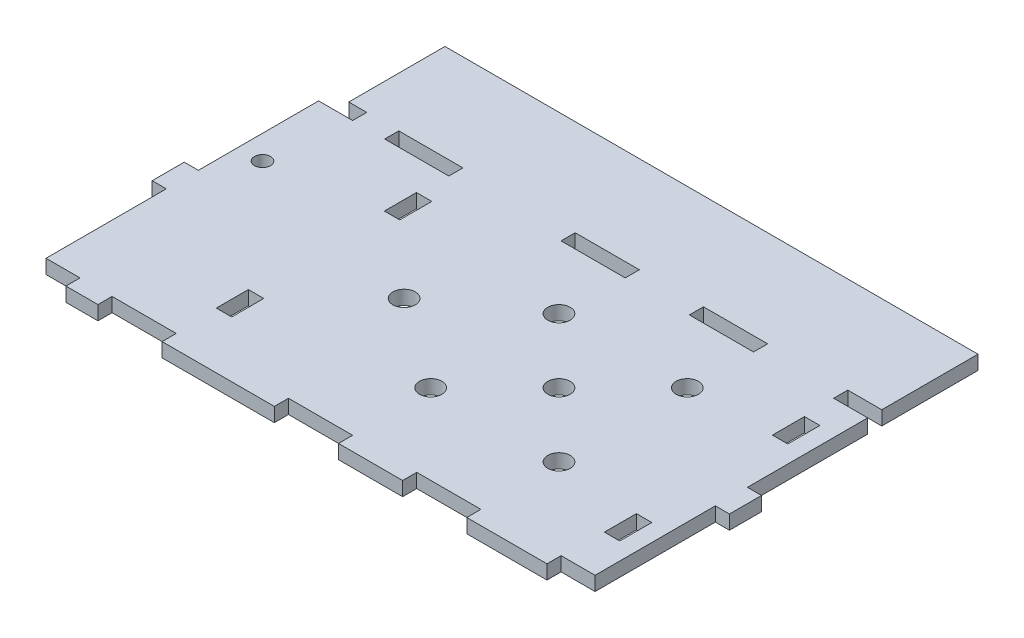
SolidWorks part; units mm, degrees
ref_plane "Front Plane" through (0, 0, 0) normal (0, 0, 1) x (1, 0, 0)
ref_plane "Top Plane" through (0, 0, 0) normal (0, 1, 0) x (1, 0, 0)
ref_plane "Right Plane" through (0, 0, 0) normal (1, 0, 0) x (0, 0, -1)
sketch "Sketch1" plane through (0, 0, 0) normal (0, 1, 0) x (1, 0, 0)
  line L0 (-108.712, 6.35) -> (-114.3, 6.35)
  line L2 (-108.712, -53.975) -> (-108.712, -6.35)
  line L4 (108.712, -53.975) -> (108.712, -6.35)
  line L5 (-108.712, -53.975) -> (108.712, 53.975) construction
  line L6 (-108.712, 53.975) -> (108.712, -53.975) construction
  line L7 (-114.3, 6.35) -> (-114.3, -6.35)
  line L8 (-114.3, -6.35) -> (-108.712, -6.35)
  line L9 (-108.712, 6.35) -> (-108.712, 53.975)
  line L10 (0, 60.325) -> (0, -60.325) construction
  line L11 (114.3, -6.35) -> (108.712, -6.35)
  line L12 (114.3, 6.35) -> (114.3, -6.35)
  line L13 (108.712, 6.35) -> (114.3, 6.35)
  line L14 (108.712, 6.35) -> (108.712, 53.975)
  line L23 (-108.712, 0) -> (106.818, 0) construction
  line L32 (-108.712, 53.975) -> (-95.25, 53.975)
  line L33 (-108.712, -53.975) -> (-95.25, -53.975)
  line L34 (-82.55, 53.975) -> (-57.15, 53.975)
  line L36 (-95.25, 53.975) -> (-95.25, 59.563)
  line L38 (-82.55, 53.975) -> (-82.55, 59.563)
  line L40 (-57.15, 53.975) -> (-57.15, 59.563)
  line L42 (-12.7, 53.975) -> (-12.7, 59.563)
  line L44 (12.7, 53.975) -> (12.7, 59.563)
  line L46 (38.1, 53.975) -> (38.1, 59.563)
  line L48 (63.5, 53.975) -> (63.5, 59.563)
  line L50 (95.25, 53.975) -> (95.25, 59.563)
  line L51 (-12.7, 53.975) -> (12.7, 53.975)
  line L52 (38.1, 53.975) -> (63.5, 53.975)
  line L53 (95.25, 53.975) -> (108.712, 53.975)
  line L54 (95.25, -53.975) -> (95.25, -59.563)
  line L55 (63.5, -59.563) -> (95.25, -59.563)
  line L56 (63.5, -53.975) -> (63.5, -59.563)
  line L57 (38.1, -53.975) -> (38.1, -59.563)
  line L58 (12.7, -59.563) -> (38.1, -59.563)
  line L59 (12.7, -53.975) -> (12.7, -59.563)
  line L60 (-12.7, -53.975) -> (-12.7, -59.563)
  line L61 (-57.15, -59.563) -> (-12.7, -59.563)
  line L62 (-57.15, -53.975) -> (-57.15, -59.563)
  line L63 (-82.55, -53.975) -> (-82.55, -59.563)
  line L64 (-95.25, -59.563) -> (-82.55, -59.563)
  line L65 (-95.25, -53.975) -> (-95.25, -59.563)
  line L66 (-82.55, -53.975) -> (-57.15, -53.975)
  line L67 (-12.7, -53.975) -> (12.7, -53.975)
  line L68 (38.1, -53.975) -> (63.5, -53.975)
  line L69 (95.25, -53.975) -> (108.712, -53.975)
  line L70 (95.25, 59.563) -> (108.712, 59.563)
  line L71 (108.712, 59.563) -> (108.712, 97.663)
  line L72 (-95.25, 59.563) -> (-102.362, 59.563)
  line L73 (-102.362, 59.563) -> (-102.362, 97.663)
  line L74 (-102.362, 97.663) -> (108.712, 97.663)
  line L75 (63.5, 59.563) -> (38.1, 59.563)
  line L76 (12.7, 59.563) -> (-12.7, 59.563)
  line L77 (-57.15, 59.563) -> (-82.55, 59.563)
  point P0 (0, 0)
  dimension "D1" = 107.95
  dimension "D3" = 12.7
  dimension "D4" = 5.588
  dimension "D5" = 5.588
  dimension "D6" = 12.7
  dimension "D7" = 25.4
  dimension "D8" = 13.462
  dimension "D9" = 38.1
extrude "Boss-Extrude1" add sketch "Sketch1" along normal blind 5.588
sketch "Sketch9" plane through (0, 5.588, 0) normal (0, 1, 0) x (1, 0, 0)
  line L0 (-108.712, -6.35) -> (-108.712, -53.975) construction
  line L1 (-57.912, -24.638) -> (-51.816, -24.638)
  line L2 (-57.912, -24.638) -> (-57.912, -37.338)
  line L3 (-57.912, -37.338) -> (-51.816, -37.338)
  line L4 (-51.816, -24.638) -> (-51.816, -37.338)
  line L5 (-82.55, -53.975) -> (-57.15, -53.975) construction
  line L6 (-57.912, 29.21) -> (-51.816, 29.21)
  line L7 (-57.912, 29.21) -> (-57.912, 41.91)
  line L8 (-57.912, 41.91) -> (-51.816, 41.91)
  line L9 (-51.816, 29.21) -> (-51.816, 41.91)
  line L10 (95.758, -24.638) -> (101.854, -24.638)
  line L11 (95.758, -24.638) -> (95.758, -37.338)
  line L12 (95.758, -37.338) -> (101.854, -37.338)
  line L13 (101.854, -24.638) -> (101.854, -37.338)
  line L14 (95.758, 41.91) -> (101.854, 41.91)
  line L15 (95.758, 41.91) -> (95.758, 29.21)
  line L16 (95.758, 29.21) -> (101.854, 29.21)
  line L17 (101.854, 41.91) -> (101.854, 29.21)
  line L18 (108.712, -53.975) -> (108.712, -6.35) construction
  line L19 (108.712, 6.35) -> (108.712, 53.975) construction
  dimension "D1" = 12.7
  dimension "D2" = 6.096
  dimension "D3" = 50.8
  dimension "D4" = 16.637
  dimension "D5" = 50.8
  dimension "D6" = 83.185
  dimension "D7" = 12.7
  dimension "D8" = 6.096
  dimension "D9" = 12.7
  dimension "D10" = 6.096
  dimension "D11" = 6.096
  dimension "D12" = 12.7
  dimension "D13" = 6.858
  dimension "D14" = 6.858
extrude "Cut-Extrude1" cut sketch "Sketch9" against normal up to next
sketch "Sketch12" plane through (0, 5.588, 0) normal (0, 1, 0) x (1, 0, 0)
  line L0 (-95.25, 53.975) -> (-108.712, 53.975) construction
  line L1 (-108.712, 53.975) -> (-108.712, 6.35) construction
  circle A0 centre (-99.187, 22.225) radius 3.175
  point P4 (-101.981, 53.975)
  dimension "D1" = 6.35
  dimension "D2" = 31.75
  dimension "D3" = 9.525
extrude "Cut-Extrude2" cut sketch "Sketch12" against normal up to next
sketch "Sketch13" plane through (0, 0, 0) normal (0, -1, 0) x (1, 0, 0)
  line L0 (38.1, -53.975) -> (63.5, -53.975) construction
  circle A0 centre (62.6731, 22.225) radius 4.445
  circle A1 centre (11.8731, 22.225) radius 4.445
  circle A2 centre (11.8731, -28.575) radius 4.445
  circle A3 centre (62.6731, -28.575) radius 4.445
  circle A4 centre (37.2731, -3.175) radius 4.445
  circle A5 centre (-24.0609, -3.175) radius 4.445
  dimension "D1" = 8.89
  dimension "D2" = 50.8
  dimension "D3" = 8.89
  dimension "D4" = 50.8
  dimension "D5" = 50.8
  dimension "D6" = 25.4
  dimension "D7" = 25.4
  dimension "D8" = 25.4
extrude "Cut-Extrude3" cut sketch "Sketch13" against normal up to next
sketch "Sketch14" plane through (0, 5.588, 0) normal (0, 1, 0) x (1, 0, 0)
  line L0 (108.712, -53.975) -> (108.712, -6.35) construction
  line L1 (102.362, -6.35) -> (105.537, -6.35)
  line L2 (102.362, -6.35) -> (102.362, 6.35)
  line L3 (102.362, 6.35) -> (105.537, 6.35)
  line L4 (105.537, -6.35) -> (105.537, 6.35)
  line L5 (108.712, -6.35) -> (114.3, -6.35) construction
  dimension "D1" = 3.175
  dimension "D2" = 12.7
  dimension "D3" = 3.175
